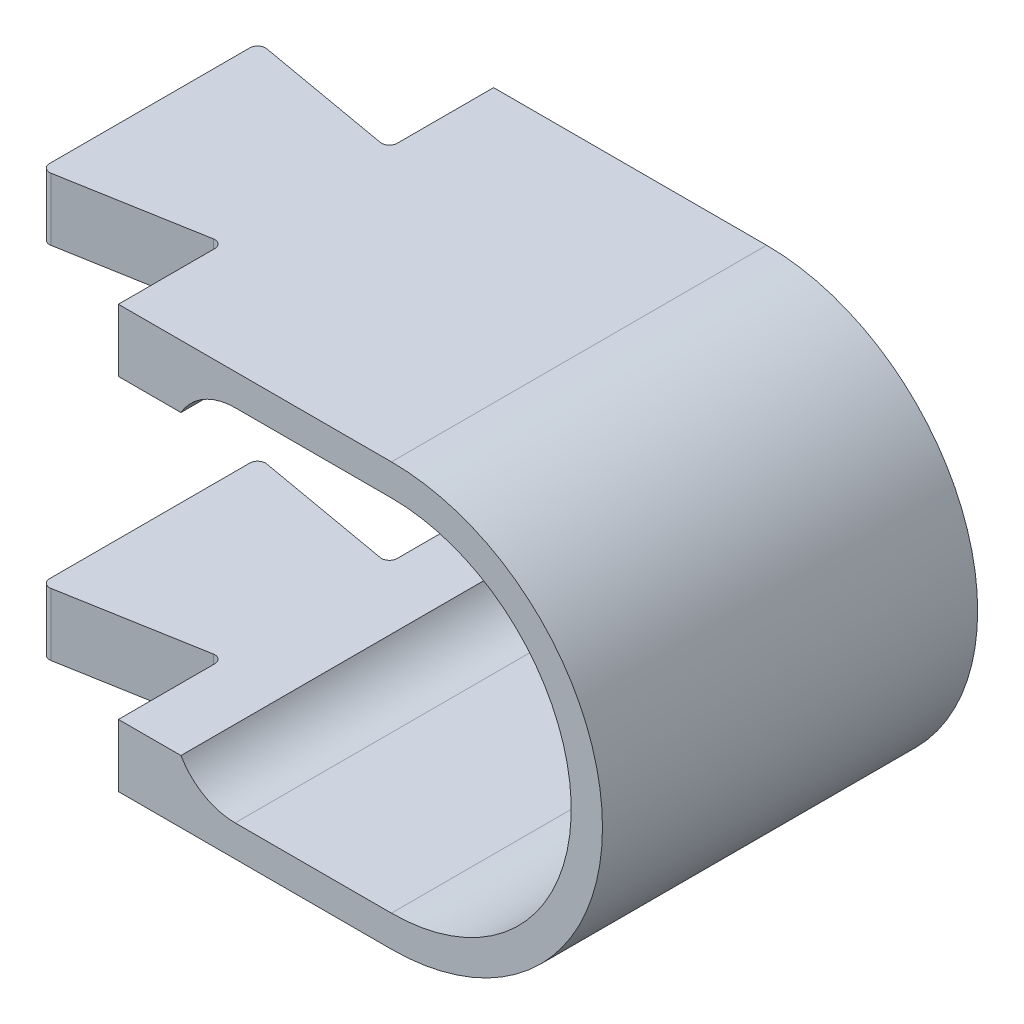
SolidWorks part; units mm, degrees
ref_plane "Front Plane" through (0, 0, 0) normal (0, 0, 1) x (1, 0, 0)
ref_plane "Top Plane" through (0, 0, 0) normal (0, 1, 0) x (1, 0, 0)
ref_plane "Right Plane" through (0, 0, 0) normal (1, 0, 0) x (0, 0, -1)
sketch "Sketch1" plane through (0, 0, 0) normal (0, 1, 0) x (1, 0, 0)
  line L0 (-15, 2.6184) -> (-20, 3.5)
  line L1 (-15, -6) -> (15, -6)
  line L2 (-15, -6) -> (-15, -2.6184)
  line L3 (-15, 6) -> (15, 6)
  line L4 (15, -6) -> (15, -2.6184)
  line L5 (-15, -6) -> (15, 6) construction
  line L6 (-15, 6) -> (15, -6) construction
  line L7 (-20, 3.5) -> (-20, -3.5)
  line L8 (-10, 0) -> (-18.3718, 0) construction
  line L9 (-15, -2.6184) -> (-20, -3.5)
  line L10 (-15, 2.6184) -> (-15, 6)
  line L11 (0, 0) -> (0, 6) construction
  line L12 (15, -2.6184) -> (20, -3.5)
  line L13 (20, 3.5) -> (20, -3.5)
  line L14 (15, 2.6184) -> (20, 3.5)
  line L15 (15, 2.6184) -> (15, 6)
  line L16 (-15, 6) -> (-25.4194, 6) construction
  point P0 (0, 0)
  point P13 (-20, 0)
  dimension "D1" = 12
  dimension "D2" = 30
  dimension "D3" = 3.5
  dimension "D4" = 80
  dimension "D5" = 5
extrude "Boss-Extrude1" add sketch "Sketch1" along normal blind 2
fillet "Fillet1" radius 0.25 8 edges at (-15, 1, 2.6184) (-20, 1, 3.5) (-20, 1, -3.5) (-15, 1, -2.6184) (15, 1, -2.6184) (20, 1, -3.5) (20, 1, 3.5) (15, 1, 2.6184)
shell "Shell1" [suppressed] thickness 1
fillet "Fillet2" [suppressed] radius 0.5
fillet "Fillet5" [suppressed] radius 1.5
sketch "Sketch2" plane through (0, 0, 0) normal (0, 0, 1) x (1, 0, 0)
  line L0 (-15, 2) -> (15, 2) construction
  line L1 (0, 0) -> (0, 2) construction
  line L2 (-14.5, 2) -> (-14.5, 5.1779)
  line L3 (-15, 0) -> (15, 0) construction
  line L4 (-14.5, 5.1779) -> (14.5, 5.1779)
  line L5 (14.5, 2) -> (14.5, 5.1779)
  spline S0 degree 3 poles (-14.5, 2) (-10.1117, 3.708) (-5.6899, 1.0248) (0, 1) knots 0 0 0 0 1 1 1 1
  spline S1 degree 3 poles (14.5, 2) (10.1117, 3.708) (5.6899, 1.0248) (0, 1) knots 0 0 0 0 1 1 1 1
  point P15 (0, 5.1779)
  dimension "D1" = 14.5
  dimension "D2" = 10
  dimension "D3" = 1
extrude "Cut-Extrude1" [suppressed] cut sketch "Sketch2" against normal mid plane 12
sketch "Sketch3" plane through (0, 2, 0) normal (0, 1, 0) x (1, 0, 0)
  line L0 (15, 6) -> (-15, 6) construction
  line L1 (-13, 6) -> (13, 6)
  line L2 (-13, 6) -> (-13, -6)
  line L3 (-13, -6) -> (13, -6)
  line L4 (13, 6) -> (13, -6)
  line L5 (-15, -6) -> (15, -6) construction
  line L6 (-15, 6) -> (-15, 2.9163) construction
  line L7 (15, 2.9163) -> (15, 6) construction
  point P8 (-15, 4.4582)
  point P11 (15, 4.4582)
  dimension "D1" = 2
  dimension "D2" = 2
extrude "Cut-Extrude2" cut sketch "Sketch3" against normal blind 1
fillet "Fillet6" radius 2 2 edges at (-13, 1, 0) (13, 1, 0)
sketch "Sketch4" plane through (0, 1, 0) normal (0, 1, 0) x (1, 0, 0)
  line L0 (-11.2679, -6) -> (11.2679, -6) construction
  line L1 (-11.2679, 6) -> (25.6358, 6)
  line L2 (-11.2679, 6) -> (-11.2679, -6)
  line L3 (-11.2679, -6) -> (25.6358, -6)
  line L4 (25.6358, 6) -> (25.6358, -6)
extrude "Cut-Extrude3" cut sketch "Sketch4" against normal mid plane 10
ref_plane "Plane1" through (0, 6.75, 0) normal (0, 1, 0) x (1, 0, 0)
sketch "Sketch6" plane through (0, 0, 0) normal (0, 0, 1) x (1, 0, 0)
  line L0 (-20.483, 6.75) -> (-11.2679, 6.75) construction
  line L1 (6.6, 6.75) -> (-6.6, 6.75) construction
  line L2 (-11.2679, 0) -> (-11.2679, 1)
  line L3 (-11.2679, 1) -> (-6.2679, 1)
  line L4 (-11.2679, 0) -> (-6.2679, 0)
  line L5 (-11.2679, 0) -> (-11.2679, 6.75) construction
  line L6 (-11.2679, 6.75) -> (-6.2679, 6.75) construction
  line L7 (-6.2679, 6.75) -> (-0.5049, 6.75) construction
  line L8 (-0.5179, 6.75) -> (0.4821, 6.75)
  arc A0 (-6.2679, 0) -> (0.4821, 6.75) centre (-6.2679, 6.75) ccw
  arc A1 (-6.2679, 1) -> (-0.5179, 6.75) centre (-6.2679, 6.75) ccw
  dimension "D3" = 5
extrude "Boss-Extrude2" add sketch "Sketch6" along normal mid plane 12
mirror "Mirror3" about plane through (0, 6.75, 0) normal (0, 1, 0) of bodies 105
